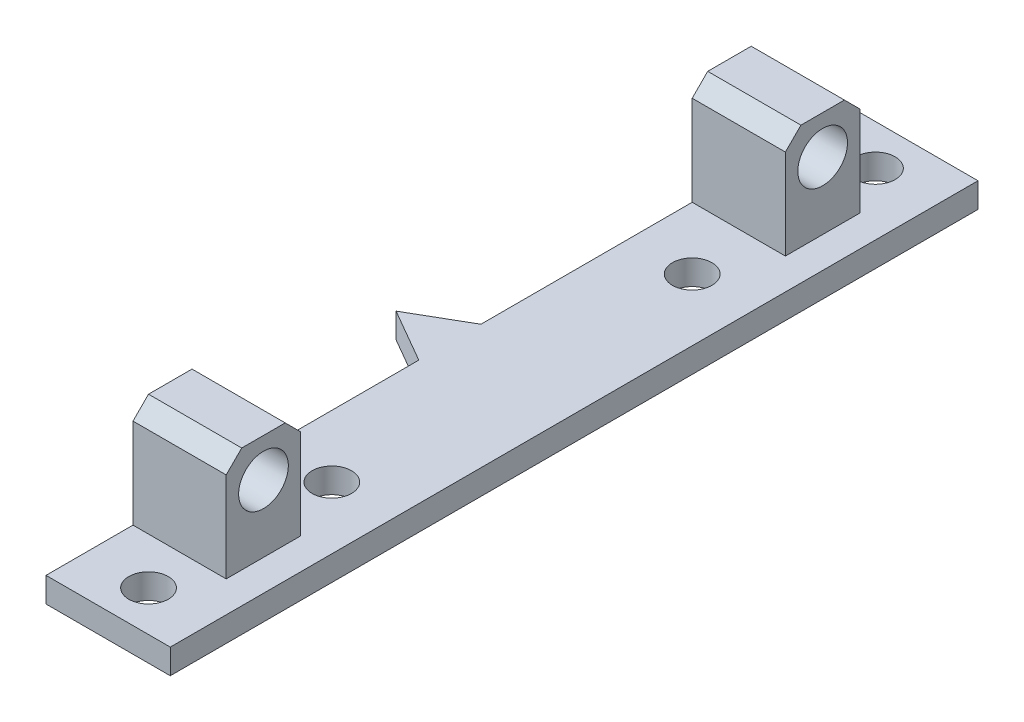
SolidWorks part; units mm, degrees
ref_plane "Front Plane" through (0, 0, 0) normal (0, 0, 1) x (1, 0, 0)
ref_plane "Top Plane" through (0, 0, 0) normal (0, 1, 0) x (1, 0, 0)
ref_plane "Right Plane" through (0, 0, 0) normal (1, 0, 0) x (0, 0, -1)
sketch "Sketch1" plane through (0, 0, 0) normal (0, 1, 0) x (1, 0, 0)
  line L1 (0, 0) -> (20, 0)
  line L2 (0, 0) -> (0, 130)
  line L3 (0, 130) -> (20, 130)
  line L4 (20, 0) -> (20, 130)
  dimension "D1" = 130
  dimension "D2" = 20
extrude "Boss-Extrude1" add sketch "Sketch1" along normal blind 4
sketch "Sketch2" plane through (0, 0, 0) normal (-1, 0, 0) x (0, 0, 1)
  line L0 (-130, 0) -> (0, 0) construction
  line L5 (-14, 18.5) -> (-16.5, 21)
  line L6 (-116, 0) -> (-104, 0)
  line L7 (-116, 0) -> (-116, 21)
  line L8 (-116, 21) -> (-104, 21)
  line L9 (-104, 0) -> (-104, 21)
  line L10 (-130, 0) -> (-116, 0) construction
  line L11 (-106.5, 21) -> (-104, 18.5)
  line L12 (-116, 18.5) -> (-113.5, 21)
  line L13 (-65, 0) -> (-65, 4) construction
  line L14 (-23.5, 21) -> (-26, 18.5)
  line L15 (-130, 4) -> (0, 4) construction
  line L16 (-26, 0) -> (-26, 21)
  line L17 (-14, 21) -> (-26, 21)
  line L18 (-14, 0) -> (-14, 21)
  line L19 (-14, 0) -> (-26, 0)
  circle A0 centre (-110, 14.8) radius 4
  circle A1 centre (-20, 14.8) radius 4
  point P10 (-110, 21)
  point P25 (-65, 4)
  point P30 (-20, 21)
  line M15 (0, 4) -> (-130, 4)
  dimension "D4" = 8
  dimension "D2" = 12
  dimension "D3" = 21
  dimension "D5" = 14.8
  dimension "D6" = 2.5
  dimension "D7" = 2.5
  dimension "D8" = 2.5
  dimension "D9" = 2.5
  dimension "D1" = 90
extrude "Boss-Extrude2" add sketch "Sketch2" against normal blind 15 contours L18 L5 L17 L14 L16 A1 M15 | L12 L7 L9 L11 L8 A0 M15 region at (0, 11.25, -14.2081) region at (0, 4.2081, -110)
sketch "Sketch3" plane through (0, 0, 0) normal (0, -1, 0) x (1, 0, 0)
  line L0 (0, -70) -> (-8.6603, -65)
  line L1 (0, -130) -> (0, 0) construction
  line L2 (-8.6603, -65) -> (0, -60)
  line L3 (0, -70) -> (0, -60)
  point P6 (0, -65)
  dimension "D1" = 10
  dimension "D2" = 10
  dimension "D3" = 10
extrude "Boss-Extrude3" add sketch "Sketch3" against normal up to surface (4 mm away) up to face at (8.3333, 4, -65)
sketch "Sketch4" plane through (0, 4, 0) normal (0, 1, 0) x (1, 0, 0)
  line L0 (10, 130) -> (10, 0) construction
  line L1 (20, 130) -> (0, 130) construction
  line L2 (0, 0) -> (20, 0) construction
  circle A0 centre (10, 123.5) radius 3.175
  circle A1 centre (10, 94) radius 3.175
  circle A2 centre (10, 36) radius 3.175
  circle A3 centre (10, 6.5) radius 3.175
  dimension "D1" = 6.35
  dimension "D2" = 6.5
  dimension "D3" = 36
  dimension "D4" = 6.5
  dimension "D5" = 36
extrude "Cut-Extrude1" cut sketch "Sketch4" against normal through all
equation "\"8mm hole\" = 8mm"
equation "\"D4@Sketch2\"= \"8mm hole\""
